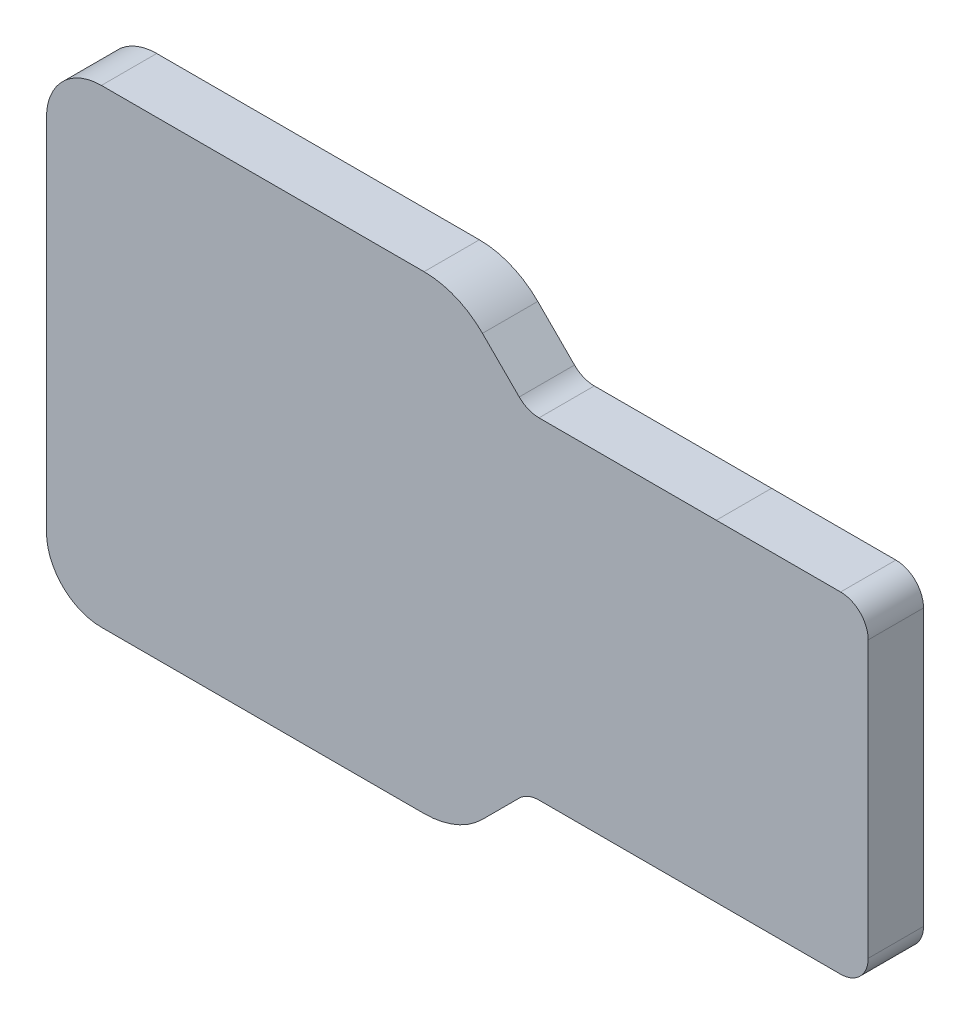
SolidWorks part; units mm, degrees
note: The reader was unsure of these and kept them because the rebuilt part matched: shared geometry of "草图2<4>".
ref_plane "前视基准面" through (0, 0, 0) normal (0, 0, 1) x (1, 0, 0)
ref_plane "上视基准面" through (0, 0, 0) normal (0, 1, 0) x (1, 0, 0)
ref_plane "右视基准面" through (0, 0, 0) normal (1, 0, 0) x (0, 0, -1)
other "Configuration Table"
sketch "草图1" plane through (0, 0, 0) normal (0, 0, 1) x (1, 0, 0)
  line L0 (-2, 5.9873) -> (-2.4911, 5.9873)
  line L4 (-5.509, 5.9873) -> (-11.9216, 5.9873)
  line L5 (-12.6377, 6.2839) -> (-13.9661, 7.6124)
  line L6 (-16.0785, 8.4873) -> (-27.7501, 8.4873)
  line L7 (-29.7374, 6.5) -> (-29.7374, -6.5)
  line L8 (-27.7501, -8.4873) -> (-16.0785, -8.4873)
  line L9 (-13.9661, -7.6124) -> (-12.6377, -6.2839)
  line L10 (-11.9216, -5.9873) -> (-5.509, -5.9873)
  line L14 (-2.4911, -5.9873) -> (-2, -5.9873)
  line L15 (-0.0127, -4) -> (-0.0127, 4)
  line L16 (-2, 4.9873) -> (-2.6929, 4.9873)
  line L17 (-3.0554, 5.1375) -> (-3.3625, 5.4446)
  line L18 (-3.7071, 5.5873) -> (-4.2929, 5.5873)
  line L19 (-4.6375, 5.4446) -> (-4.9446, 5.1375)
  line L20 (-5.3069, 4.9873) -> (-11.9216, 4.9873)
  line L21 (-13.3448, 5.5768) -> (-14.6732, 6.9052)
  line L22 (-16.0785, 7.4873) -> (-27.7501, 7.4873)
  line L23 (-28.7374, 6.5) -> (-28.7374, -6.5)
  line L24 (-27.7501, -7.4873) -> (-16.0785, -7.4873)
  line L25 (-14.6732, -6.9052) -> (-13.3448, -5.5768)
  line L26 (-11.9216, -4.9873) -> (-5.3071, -4.9873)
  line L27 (-4.9446, -5.1375) -> (-4.6375, -5.4446)
  line L28 (-4.2929, -5.5873) -> (-3.7071, -5.5873)
  line L29 (-3.3625, -5.4446) -> (-3.0554, -5.1375)
  line L30 (-2.6929, -4.9873) -> (-2, -4.9873)
  line L31 (-1.0127, -4) -> (-1.0127, 4)
  line L32 (-2, 4.9873) -> (-2.6929, 4.9873) construction
  line L33 (-3.0554, 5.1375) -> (-3.3625, 5.4446) construction
  line L34 (-3.7071, 5.5873) -> (-4.2929, 5.5873) construction
  line L35 (-4.6375, 5.4446) -> (-4.9446, 5.1375) construction
  line L36 (-5.3069, 4.9873) -> (-11.9216, 4.9873) construction
  line L37 (-13.3448, 5.5768) -> (-14.6732, 6.9052) construction
  line L38 (-16.0785, 7.4873) -> (-27.7501, 7.4873) construction
  line L39 (-28.7374, 6.5) -> (-28.7374, -6.5) construction
  line L40 (-27.7501, -7.4873) -> (-16.0785, -7.4873) construction
  line L41 (-14.6732, -6.9052) -> (-13.3448, -5.5768) construction
  line L42 (-11.9216, -4.9873) -> (-5.3071, -4.9873) construction
  line L43 (-4.9446, -5.1375) -> (-4.6375, -5.4446) construction
  line L44 (-4.2929, -5.5873) -> (-3.7071, -5.5873) construction
  line L45 (-3.3625, -5.4446) -> (-3.0554, -5.1375) construction
  line L46 (-2.6929, -4.9873) -> (-2, -4.9873) construction
  line L47 (-1.0127, -4) -> (-1.0127, 4) construction
  line L48 (-2.4911, 5.9873) -> (-2.6554, 6.1517) construction
  line L49 (-3.7071, 6.5873) -> (-4.2929, 6.5873) construction
  line L50 (-5.3446, 6.1517) -> (-5.509, 5.9873) construction
  line L51 (-2.6554, -6.1517) -> (-2.4911, -5.9873) construction
  line L52 (-4.2929, -6.5873) -> (-3.7071, -6.5873) construction
  line L53 (-5.509, -5.9873) -> (-5.3446, -6.1517) construction
  line L54 (-5.509, -5.9873) -> (-2.4911, -5.9873)
  line L55 (-2, -5.9873) -> (-0.0127, -5.9873)
  line L56 (-0.0127, -5.9873) -> (-0.0127, -4)
  line L57 (-0.0127, 4) -> (-0.0127, 5.9873)
  line L58 (-0.0127, 5.9873) -> (-2, 5.9873)
  line L59 (-2.4911, 5.9873) -> (-5.509, 5.9873)
  arc A1 (-2.4911, 5.9873) -> (-2.4911, 5.9873) centre (-2.4911, 5.9873) ccw
  arc A4 (-5.509, 5.9873) -> (-5.509, 5.9873) centre (-5.509, 5.9873) ccw
  arc A5 (-12.6377, 6.2839) -> (-11.9216, 5.9873) centre (-11.9216, 7) ccw
  arc A6 (-13.9661, 7.6124) -> (-16.0785, 8.4873) centre (-16.0785, 5.5) ccw
  arc A7 (-27.7501, 8.4873) -> (-29.7374, 6.5) centre (-27.7501, 6.5) ccw
  arc A8 (-29.7374, -6.5) -> (-27.7501, -8.4873) centre (-27.7501, -6.5) ccw
  arc A9 (-16.0785, -8.4873) -> (-13.9661, -7.6124) centre (-16.0785, -5.5) ccw
  arc A10 (-11.9216, -5.9873) -> (-12.6377, -6.2839) centre (-11.9216, -7) ccw
  arc A11 (-5.509, -5.9873) -> (-5.509, -5.9873) centre (-5.509, -5.9873) ccw
  arc A14 (-2.4911, -5.9873) -> (-2.4911, -5.9873) centre (-2.4911, -5.9873) ccw
  arc A16 (-1.0127, 4) -> (-2, 4.9873) centre (-2, 4) ccw
  arc A17 (-3.0554, 5.1375) -> (-2.6929, 4.9873) centre (-2.6929, 5.5) ccw
  arc A18 (-3.3625, 5.4446) -> (-3.7071, 5.5873) centre (-3.7071, 5.1) ccw
  arc A19 (-4.2929, 5.5873) -> (-4.6375, 5.4446) centre (-4.2929, 5.1) ccw
  arc A20 (-5.3069, 4.9873) -> (-4.9446, 5.1375) centre (-5.3071, 5.5) ccw
  arc A21 (-13.3448, 5.5768) -> (-11.9216, 4.9873) centre (-11.9216, 7) ccw
  arc A22 (-14.6732, 6.9052) -> (-16.0785, 7.4873) centre (-16.0785, 5.5) ccw
  arc A23 (-27.7501, 7.4873) -> (-28.7374, 6.5) centre (-27.7501, 6.5) ccw
  arc A24 (-28.7374, -6.5) -> (-27.7501, -7.4873) centre (-27.7501, -6.5) ccw
  arc A25 (-16.0785, -7.4873) -> (-14.6732, -6.9052) centre (-16.0785, -5.5) ccw
  arc A26 (-11.9216, -4.9873) -> (-13.3448, -5.5768) centre (-11.9216, -7) ccw
  arc A27 (-4.9446, -5.1375) -> (-5.3071, -4.9873) centre (-5.3071, -5.5) ccw
  arc A28 (-4.6375, -5.4446) -> (-4.2929, -5.5873) centre (-4.2929, -5.1) ccw
  arc A29 (-3.7071, -5.5873) -> (-3.3625, -5.4446) centre (-3.7071, -5.1) ccw
  arc A30 (-2.6929, -4.9873) -> (-3.0554, -5.1375) centre (-2.6929, -5.5) ccw
  arc A31 (-2, -4.9873) -> (-1.0127, -4) centre (-2, -4) ccw
  arc A32 (-1.0127, 4) -> (-2, 4.9873) centre (-2, 4) ccw construction
  arc A33 (-3.0554, 5.1375) -> (-2.6929, 4.9873) centre (-2.6929, 5.5) ccw construction
  arc A34 (-3.3625, 5.4446) -> (-3.7071, 5.5873) centre (-3.7071, 5.1) ccw construction
  arc A35 (-4.2929, 5.5873) -> (-4.6375, 5.4446) centre (-4.2929, 5.1) ccw construction
  arc A36 (-5.3069, 4.9873) -> (-4.9446, 5.1375) centre (-5.3071, 5.5) ccw construction
  arc A37 (-13.3448, 5.5768) -> (-11.9216, 4.9873) centre (-11.9216, 7) ccw construction
  arc A38 (-14.6732, 6.9052) -> (-16.0785, 7.4873) centre (-16.0785, 5.5) ccw construction
  arc A39 (-27.7501, 7.4873) -> (-28.7374, 6.5) centre (-27.7501, 6.5) ccw construction
  arc A40 (-28.7374, -6.5) -> (-27.7501, -7.4873) centre (-27.7501, -6.5) ccw construction
  arc A41 (-16.0785, -7.4873) -> (-14.6732, -6.9052) centre (-16.0785, -5.5) ccw construction
  arc A42 (-11.9216, -4.9873) -> (-13.3448, -5.5768) centre (-11.9216, -7) ccw construction
  arc A43 (-4.9446, -5.1375) -> (-5.3071, -4.9873) centre (-5.3071, -5.5) ccw construction
  arc A44 (-4.6375, -5.4446) -> (-4.2929, -5.5873) centre (-4.2929, -5.1) ccw construction
  arc A45 (-3.7071, -5.5873) -> (-3.3625, -5.4446) centre (-3.7071, -5.1) ccw construction
  arc A46 (-2.6929, -4.9873) -> (-3.0554, -5.1375) centre (-2.6929, -5.5) ccw construction
  arc A47 (-2, -4.9873) -> (-1.0127, -4) centre (-2, -4) ccw construction
  arc A48 (-2.6554, 6.1517) -> (-3.7071, 6.5873) centre (-3.7071, 5.1) ccw construction
  arc A49 (-4.2929, 6.5873) -> (-5.3446, 6.1517) centre (-4.2929, 5.1) ccw construction
  arc A50 (-3.7071, -6.5873) -> (-2.6554, -6.1517) centre (-3.7071, -5.1) ccw construction
  arc A51 (-5.3446, -6.1517) -> (-4.2929, -6.5873) centre (-4.2929, -5.1) ccw construction
  arc A52 (-2, -5.9873) -> (-0.0127, -4) centre (-2, -4) ccw construction
  arc A53 (-0.0127, 4) -> (-2, 5.9873) centre (-2, 4) ccw construction
  dimension "D1" = 0
  dimension "D2" = 1
extrude "凸台-拉伸1" add sketch "草图1" along normal blind 1 contours A10 L10 L54 L14 L55 L56 L15 L57 L58 L0 L59 L4 A5 L5 A6 L6 A7 L7 A8 L8 A9 L9
sketch "草图2" plane through (0, 0, 0) normal (0, 0, -1) x (-1, 0, 0)
  line L36 (1.0127, 4) -> (1.0127, -4)
  line L37 (2, -4.9873) -> (2.6929, -4.9873)
  line L38 (3.0554, -5.1375) -> (3.3625, -5.4446)
  line L39 (3.7071, -5.5873) -> (4.2929, -5.5873)
  line L40 (4.6375, -5.4446) -> (4.9446, -5.1375)
  line L41 (5.3071, -4.9873) -> (11.9216, -4.9873)
  line L42 (13.3448, -5.5768) -> (14.6732, -6.9052)
  line L43 (16.0785, -7.4873) -> (27.7501, -7.4873)
  line L44 (28.7374, -6.5) -> (28.7374, 6.5)
  line L45 (27.7501, 7.4873) -> (16.0785, 7.4873)
  line L46 (14.6732, 6.9052) -> (13.3448, 5.5768)
  line L47 (11.9216, 4.9873) -> (5.3069, 4.9873)
  line L48 (4.9446, 5.1375) -> (4.6375, 5.4446)
  line L49 (4.2929, 5.5873) -> (3.7071, 5.5873)
  line L50 (3.3625, 5.4446) -> (3.0554, 5.1375)
  line L51 (2.6929, 4.9873) -> (2, 4.9873)
  line L52 (1.0127, 4) -> (1.0127, -4) construction
  line L53 (2, -4.9873) -> (2.6929, -4.9873) construction
  line L54 (3.0554, -5.1375) -> (3.3625, -5.4446) construction
  line L55 (3.7071, -5.5873) -> (4.2929, -5.5873) construction
  line L56 (4.6375, -5.4446) -> (4.9446, -5.1375) construction
  line L57 (5.3071, -4.9873) -> (11.9216, -4.9873) construction
  line L58 (13.3448, -5.5768) -> (14.6732, -6.9052) construction
  line L59 (16.0785, -7.4873) -> (27.7501, -7.4873) construction
  line L60 (28.7374, -6.5) -> (28.7374, 6.5) construction
  line L61 (27.7501, 7.4873) -> (16.0785, 7.4873) construction
  line L62 (14.6732, 6.9052) -> (13.3448, 5.5768) construction
  line L63 (11.9216, 4.9873) -> (5.3069, 4.9873) construction
  line L64 (4.9446, 5.1375) -> (4.6375, 5.4446) construction
  line L65 (4.2929, 5.5873) -> (3.7071, 5.5873) construction
  line L66 (3.3625, 5.4446) -> (3.0554, 5.1375) construction
  line L67 (2.6929, 4.9873) -> (2, 4.9873) construction
  line L68 (0.9127, 4) -> (0.9127, -4)
  line L69 (2, -5.0873) -> (2.6929, -5.0873)
  line L70 (2.9847, -5.2082) -> (3.2918, -5.5153)
  line L71 (3.7071, -5.6873) -> (4.2929, -5.6873)
  line L72 (4.7082, -5.5153) -> (5.0153, -5.2082)
  line L73 (5.3071, -5.0873) -> (11.9216, -5.0873)
  line L74 (13.2741, -5.6475) -> (14.6025, -6.976)
  line L75 (16.0785, -7.5873) -> (27.7501, -7.5873)
  line L76 (28.8374, -6.5) -> (28.8374, 6.5)
  line L77 (27.7501, 7.5873) -> (16.0785, 7.5873)
  line L78 (14.6025, 6.976) -> (13.2741, 5.6475)
  line L79 (11.9216, 5.0873) -> (5.3069, 5.0873)
  line L80 (5.0153, 5.2082) -> (4.7082, 5.5153)
  line L81 (4.2929, 5.6873) -> (3.7071, 5.6873)
  line L82 (3.2918, 5.5153) -> (2.9847, 5.2082)
  line L83 (2.6929, 5.0873) -> (2, 5.0873)
  arc A28 (1.0127, -4) -> (2, -4.9873) centre (2, -4) ccw
  arc A29 (3.0554, -5.1375) -> (2.6929, -4.9873) centre (2.6929, -5.5) ccw
  arc A30 (3.3625, -5.4446) -> (3.7071, -5.5873) centre (3.7071, -5.1) ccw
  arc A31 (4.2929, -5.5873) -> (4.6375, -5.4446) centre (4.2929, -5.1) ccw
  arc A32 (5.3071, -4.9873) -> (4.9446, -5.1375) centre (5.3071, -5.5) ccw
  arc A33 (13.3448, -5.5768) -> (11.9216, -4.9873) centre (11.9216, -7) ccw
  arc A34 (14.6732, -6.9052) -> (16.0785, -7.4873) centre (16.0785, -5.5) ccw
  arc A35 (27.7501, -7.4873) -> (28.7374, -6.5) centre (27.7501, -6.5) ccw
  arc A36 (28.7374, 6.5) -> (27.7501, 7.4873) centre (27.7501, 6.5) ccw
  arc A37 (16.0785, 7.4873) -> (14.6732, 6.9052) centre (16.0785, 5.5) ccw
  arc A38 (11.9216, 4.9873) -> (13.3448, 5.5768) centre (11.9216, 7) ccw
  arc A39 (4.9446, 5.1375) -> (5.3069, 4.9873) centre (5.3071, 5.5) ccw
  arc A40 (4.6375, 5.4446) -> (4.2929, 5.5873) centre (4.2929, 5.1) ccw
  arc A41 (3.7071, 5.5873) -> (3.3625, 5.4446) centre (3.7071, 5.1) ccw
  arc A42 (2.6929, 4.9873) -> (3.0554, 5.1375) centre (2.6929, 5.5) ccw
  arc A43 (2, 4.9873) -> (1.0127, 4) centre (2, 4) ccw
  arc A44 (1.0127, -4) -> (2, -4.9873) centre (2, -4) ccw construction
  arc A45 (3.0554, -5.1375) -> (2.6929, -4.9873) centre (2.6929, -5.5) ccw construction
  arc A46 (3.3625, -5.4446) -> (3.7071, -5.5873) centre (3.7071, -5.1) ccw construction
  arc A47 (4.2929, -5.5873) -> (4.6375, -5.4446) centre (4.2929, -5.1) ccw construction
  arc A48 (5.3071, -4.9873) -> (4.9446, -5.1375) centre (5.3071, -5.5) ccw construction
  arc A49 (13.3448, -5.5768) -> (11.9216, -4.9873) centre (11.9216, -7) ccw construction
  arc A50 (14.6732, -6.9052) -> (16.0785, -7.4873) centre (16.0785, -5.5) ccw construction
  arc A51 (27.7501, -7.4873) -> (28.7374, -6.5) centre (27.7501, -6.5) ccw construction
  arc A52 (28.7374, 6.5) -> (27.7501, 7.4873) centre (27.7501, 6.5) ccw construction
  arc A53 (16.0785, 7.4873) -> (14.6732, 6.9052) centre (16.0785, 5.5) ccw construction
  arc A54 (11.9216, 4.9873) -> (13.3448, 5.5768) centre (11.9216, 7) ccw construction
  arc A55 (4.9446, 5.1375) -> (5.3069, 4.9873) centre (5.3071, 5.5) ccw construction
  arc A56 (4.6375, 5.4446) -> (4.2929, 5.5873) centre (4.2929, 5.1) ccw construction
  arc A57 (3.7071, 5.5873) -> (3.3625, 5.4446) centre (3.7071, 5.1) ccw construction
  arc A58 (2.6929, 4.9873) -> (3.0554, 5.1375) centre (2.6929, 5.5) ccw construction
  arc A59 (2, 4.9873) -> (1.0127, 4) centre (2, 4) ccw construction
  arc A60 (14.0974, -5.1232) -> (16.0974, -5.1232) centre (15.0974, -5.1232) ccw construction
  arc A61 (16.0974, -5.1232) -> (14.0974, -5.1232) centre (15.0974, -5.1232) ccw construction
  arc A62 (14.0974, -5.1232) -> (16.0974, -5.1232) centre (15.0974, -5.1232) ccw construction
  arc A63 (16.0974, -5.1232) -> (14.0974, -5.1232) centre (15.0974, -5.1232) ccw construction
  arc A64 (14.1974, -5.1232) -> (15.9974, -5.1232) centre (15.0974, -5.1232) ccw
  arc A65 (15.9974, -5.1232) -> (14.1974, -5.1232) centre (15.0974, -5.1232) ccw
  arc A66 (0.9127, -4) -> (2, -5.0873) centre (2, -4) ccw
  arc A67 (2.9847, -5.2082) -> (2.6929, -5.0873) centre (2.6929, -5.5) ccw
  arc A68 (3.2918, -5.5153) -> (3.7071, -5.6873) centre (3.7071, -5.1) ccw
  arc A69 (4.2929, -5.6873) -> (4.7082, -5.5153) centre (4.2929, -5.1) ccw
  arc A70 (5.3071, -5.0873) -> (5.0153, -5.2082) centre (5.3071, -5.5) ccw
  arc A71 (13.2741, -5.6475) -> (11.9216, -5.0873) centre (11.9216, -7) ccw
  arc A72 (14.6025, -6.976) -> (16.0785, -7.5873) centre (16.0785, -5.5) ccw
  arc A73 (27.7501, -7.5873) -> (28.8374, -6.5) centre (27.7501, -6.5) ccw
  arc A74 (28.8374, 6.5) -> (27.7501, 7.5873) centre (27.7501, 6.5) ccw
  arc A75 (16.0785, 7.5873) -> (14.6025, 6.976) centre (16.0785, 5.5) ccw
  arc A76 (11.9216, 5.0873) -> (13.2741, 5.6475) centre (11.9216, 7) ccw
  arc A77 (5.0153, 5.2082) -> (5.3069, 5.0873) centre (5.3071, 5.5) ccw
  arc A78 (4.7082, 5.5153) -> (4.2929, 5.6873) centre (4.2929, 5.1) ccw
  arc A79 (3.7071, 5.6873) -> (3.2918, 5.5153) centre (3.7071, 5.1) ccw
  arc A80 (2.6929, 5.0873) -> (2.9847, 5.2082) centre (2.6929, 5.5) ccw
  arc A81 (2, 5.0873) -> (0.9127, 4) centre (2, 4) ccw
  dimension "D1" = 0.1
  dimension "D2" = 0
  dimension "D4" = 0.1
extrude "凸台-拉伸2" add sketch "草图2" along normal blind 1
extrude "凸台-拉伸3" add sketch "草图2<4>" along normal blind 2 contours A64 A65
sketch "草图2<4>" plane through (0, 0, 0) normal (0, 0, -1) x (-1, 0, 0) same geometry as "草图2"
fillet "圆角1" radius 1 2 edges at (-0.0127, 5.9873, 0) (-0.0127, -5.9873, 0)
